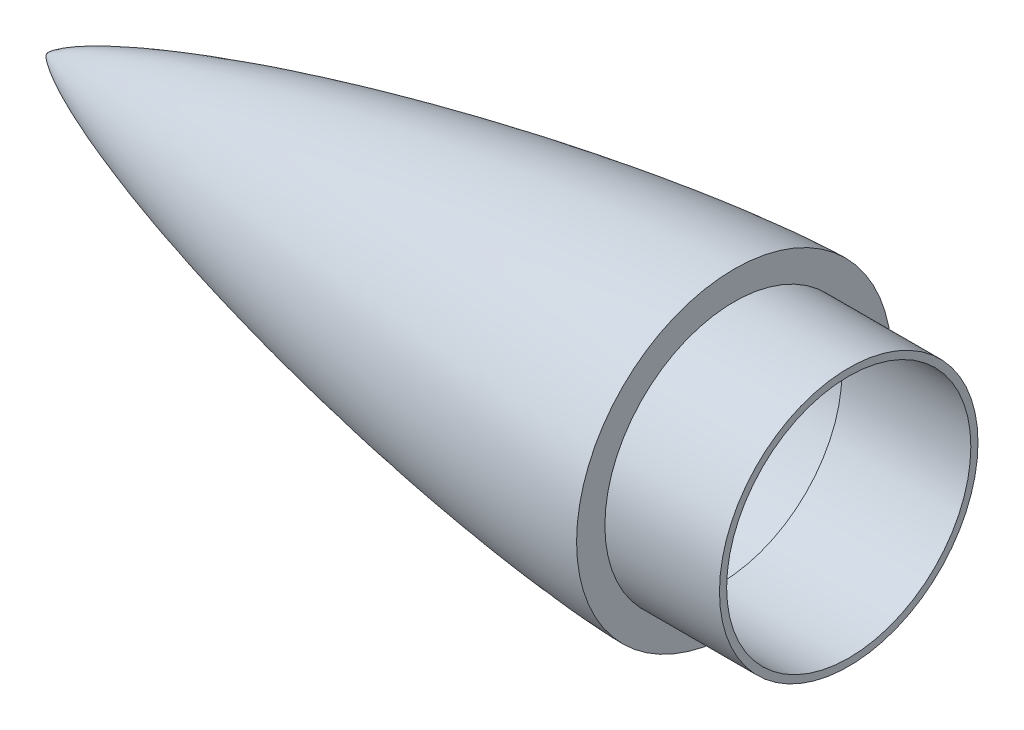
SolidWorks part; units mm, degrees
ref_plane "Front Plane" through (0, 0, 0) normal (0, 0, 1) x (1, 0, 0)
ref_plane "Top Plane" through (0, 0, 0) normal (0, 1, 0) x (1, 0, 0)
ref_plane "Right Plane" through (0, 0, 0) normal (1, 0, 0) x (0, 0, -1)
sketch "Sketch1" plane through (0, 0, 0) normal (0, 0, 1) x (1, 0, 0)
  line L0 (0, 0) -> (152.4, 0)
  line L1 (152.4, 0) -> (152.4, 34.925)
  spline S0 degree 4 poles (0, 0) (0.0018, 0.0091) (0.0067, 0.0271) (0.0216, 0.0613) (0.0511, 0.115) (0.0929, 0.1786) (0.1619, 0.2704) (0.2717, 0.3986) (0.4559, 0.588) (0.7811, 0.8805) (1.3435, 1.3221) (2.3181, 1.9889) (4.0085, 2.9942) (6.678, 4.3729) (11.167, 6.404) (17.5515, 8.9106) (25.5104, 11.6665) (34.7357, 14.5205) (44.2447, 17.1938) (53.8087, 19.6618) (63.4172, 21.9502) (73.0633, 24.0739) (82.7424, 26.0419) (92.4512, 27.8577) (102.1873, 29.5207) (111.9491, 31.0256) (121.7358, 32.3602) (131.5466, 33.5052) (139.6812, 34.2625) (146.1277, 34.7092) (150.1163, 34.879) (151.6386, 34.9194) (152.4, 34.925) knots 0 0 0 0 0 0.000236 0.000472 0.000944 0.001554 0.002166 0.003385 0.005227 0.008256 0.013259 0.021523 0.035183 0.058148 0.089487 0.146543 0.20922 0.271897 0.334574 0.397252 0.459929 0.522606 0.585283 0.64796 0.710638 0.773315 0.835992 0.898669 0.961346 0.980673 1 1 1 1 1 construction
  spline S1 degree 4 poles (0, 0) (0.0018, 0.0091) (0.0067, 0.0271) (0.0216, 0.0613) (0.0511, 0.115) (0.0929, 0.1786) (0.1619, 0.2704) (0.2717, 0.3986) (0.4559, 0.588) (0.7811, 0.8805) (1.3435, 1.3221) (2.3181, 1.9889) (4.0085, 2.9942) (6.678, 4.3729) (11.167, 6.404) (17.5515, 8.9106) (25.5104, 11.6665) (34.7357, 14.5205) (44.2447, 17.1938) (53.8087, 19.6618) (63.4172, 21.9502) (73.0633, 24.0739) (82.7424, 26.0419) (92.4512, 27.8577) (102.1873, 29.5207) (111.9491, 31.0256) (121.7358, 32.3602) (131.5466, 33.5052) (139.6812, 34.2625) (146.1277, 34.7092) (150.1163, 34.879) (151.6386, 34.9194) (152.4, 34.925) knots 0 0 0 0 0 0.000236 0.000472 0.000944 0.001554 0.002166 0.003385 0.005227 0.008256 0.013259 0.021523 0.035183 0.058148 0.089487 0.146543 0.20922 0.271897 0.334574 0.397252 0.459929 0.522606 0.585283 0.64796 0.710638 0.773315 0.835992 0.898669 0.961346 0.980673 1 1 1 1 1
  point P0 (0, 0)
revolve "Revolve1" add sketch "Sketch1" angle 360 about L0
shell "Shell1" thickness 3.175 removed face at (152.4, 0, 34.925)
sketch "Sketch2" plane through (152.4, 0, 0) normal (1, 0, 0) x (0, 0, -1)
  circle A0 centre (0, 0) radius 33.02
ref_plane "Plane1" through (149.225, 0, 0) normal (1, 0, 0) x (0, 0, -1)
sketch "Sketch3" plane through (149.225, 0, 0) normal (1, 0, 0) x (0, 0, -1)
  circle A1 centre (0, 0) radius 31.7499
  circle A2 centre (0, 0) radius 30.1624
  dimension "D1" = 1.5875
extrude "Boss-Extrude1" add sketch "Sketch3" along normal blind 3.175
ref_plane "Plane2" through (177.8, 0, 0) normal (1, 0, 0) x (0, 0, -1)
sketch "Sketch4" plane through (177.8, 0, 0) normal (1, 0, 0) x (0, 0, -1)
  circle A0 centre (0, 0) radius 28.6512
ref_plane "Plane3" through (149.225, 0, 0) normal (1, 0, 0) x (0, 0, -1)
sketch "Sketch5" plane through (149.225, 0, 0) normal (1, 0, 0) x (0, 0, -1)
  circle A0 centre (0, 0) radius 27.0637
  circle A1 centre (0, 0) radius 33.02
extrude "Boss-Extrude4" add sketch "Sketch5" along normal blind 3.175 contours A1 A0 region at (149.225, 0, 32.0861)
extrude "Boss-Extrude5" add sketch "Sketch4" against normal up to surface (25.4 mm away)
sketch "Sketch9" plane through (177.8, 0, 0) normal (1, 0, 0) x (0, 0, -1)
  circle A0 centre (0, 0) radius 27.0637
extrude "Cut-Extrude1" cut sketch "Sketch9" against normal up to surface (25.4 mm away)
